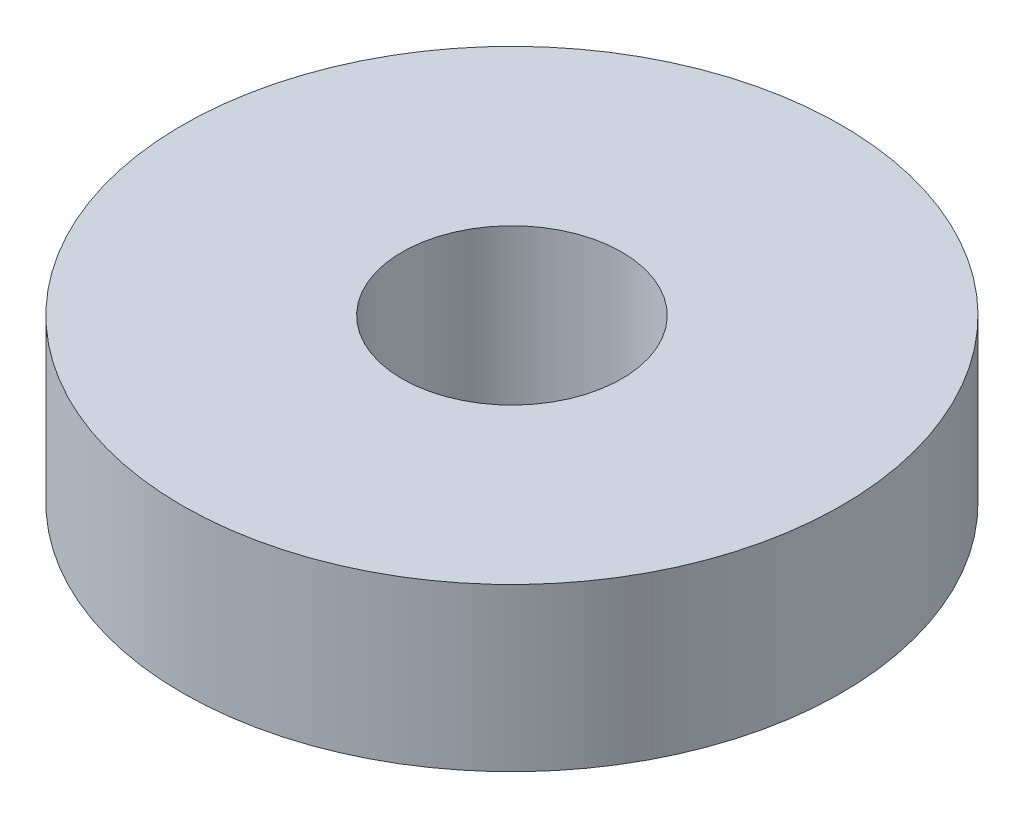
SolidWorks part; units mm, degrees
material "Plain Carbon Steel"
ref_plane "Front Plane" through (0, 0, 0) normal (0, 0, 1) x (1, 0, 0)
ref_plane "Top Plane" through (0, 0, 0) normal (0, 1, 0) x (1, 0, 0)
ref_plane "Right Plane" through (0, 0, 0) normal (1, 0, 0) x (0, 0, -1)
sketch "Sketch1" plane through (0, 0, 0) normal (0, 1, 0) x (1, 0, 0)
  circle A0 centre (0, 0) radius 22.5
  circle A1 centre (0, 0) radius 7.5
  dimension "D1" = 45
  dimension "D2" = 15
extrude "Boss-Extrude1" add sketch "Sketch1" along normal blind 11.07
